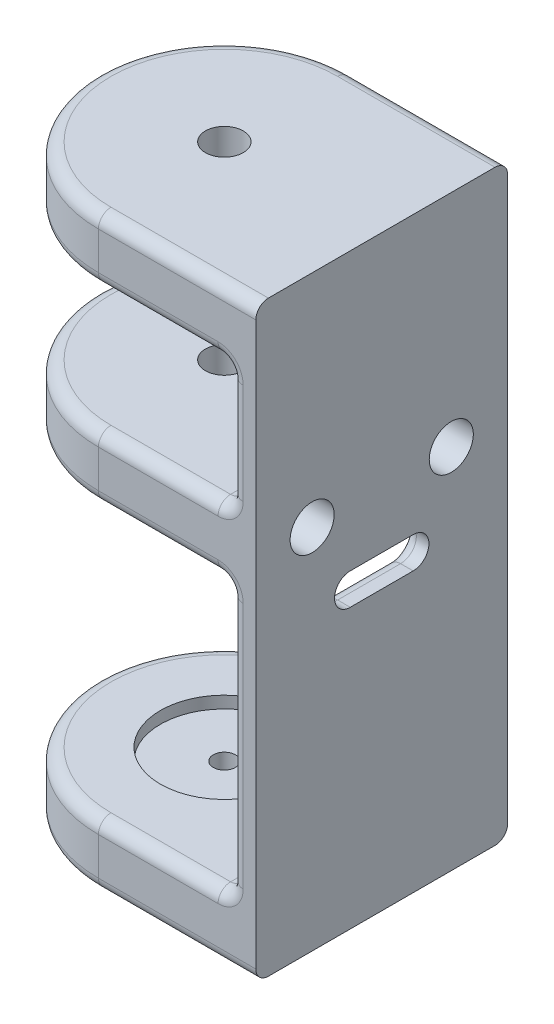
SolidWorks part; units mm, degrees
ref_plane "Front Plane" through (0, 0, 0) normal (0, 0, 1) x (1, 0, 0)
ref_plane "Top Plane" through (0, 0, 0) normal (0, 1, 0) x (1, 0, 0)
ref_plane "Right Plane" through (0, 0, 0) normal (1, 0, 0) x (0, 0, -1)
sketch "Sketch2" plane through (0, 0, 0) normal (0, 1, 0) x (1, 0, 0)
  line L1 (-2, -20) -> (2, -20)
  line L2 (-2, -20) -> (-2, 20)
  line L3 (-2, 20) -> (2, 20)
  line L4 (2, -20) -> (2, 20)
  line L5 (-2, -20) -> (2, 20) construction
  line L6 (-2, 20) -> (2, -20) construction
  point P0 (0, 0)
  dimension "D1" = 4
  dimension "D2" = 40
extrude "Boss-Extrude1" add sketch "Sketch2" along normal blind 93.3
sketch "Sketch1" plane through (0, 93.3, 0) normal (0, 1, 0) x (1, 0, 0)
  line L0 (-2, 20) -> (-2, -20) construction
  line L1 (-23, -20) -> (-2, -20)
  line L3 (-23, 20) -> (-2, 20)
  line L4 (-2, -20) -> (-2, 20)
  line L5 (-23, -20) -> (-2, 20) construction
  line L6 (-23, 20) -> (-2, -20) construction
  line L7 (2, 20) -> (-2, 20) construction
  arc A0 (-23, -20) -> (-23, 20) centre (-23, 0) cw
  point P0 (-12.5, 0)
  dimension "D2" = 40
  dimension "D3" = 21
extrude "Boss-Extrude2" add sketch "Sketch1" against normal blind 10 separate body
sketch "Sketch4" plane through (0, 93.3, 0) normal (0, 1, 0) x (1, 0, 0)
  circle A0 centre (-23, 0) radius 3
  dimension "D1" = 6
extrude "Cut-Extrude4" cut sketch "Sketch4" against normal up to surface (10 mm away) up to face at (-17.5, 83.3, 0)
ref_plane "Plane1" through (0, 46.65, 0) normal (0, 1, 0) x (1, 0, 0)
mirror "Mirror8" about plane through (0, 46.65, 0) normal (0, 1, 0) of "Boss-Extrude2"
ref_plane "Plane3" through (0, 73.3, 0) normal (0, 1, 0) x (1, 0, 0)
mirror "Mirror10" about plane through (0, 73.3, 0) normal (0, 1, 0) of "Boss-Extrude2", "Cut-Extrude4"
combine bodies "Combine2" operation type add bodies to combine 109 107
sketch "Sketch3" plane through (0, 10, 0) normal (0, 1, 0) x (1, 0, 0)
  circle A0 centre (-23, 0) radius 3 construction
  circle A3 centre (-23, 0) radius 10.15
  dimension "D1" = 20.3
extrude "Cut-Extrude3" cut sketch "Sketch3" against normal blind 1.9
sketch "Sketch6" plane through (0, 8.1, 0) normal (0, 1, 0) x (1, 0, 0)
  circle A0 centre (-23, 0) radius 1.75
  circle A3 centre (-23, 0) radius 3 construction
  dimension "D1" = 3.5
extrude "Cut-Extrude6" cut sketch "Sketch6" against normal through all
fillet "Fillet2" radius 2 26 edges at (-2, 63.3, 0) (-2, 10, 0) (-2, 53.3, 0) (-10.5, 0, -20) (-10.5, 0, 20) (-10.5, 93.3, -20) (-10.5, 93.3, 20) (-43, 10, 0) (-43, 53.3, 0) (-43, 63.3, 0) (-12.5, 53.3, 20) (-12.5, 10, 20) (-12.5, 10, -20) (-12.5, 53.3, -20) (-12.5, 63.3, 20) (-12.5, 63.3, -20) (-43, 0, 0) (-2, 31.65, 20) (-2, 31.65, -20) (-43, 93.3, 0) (-43, 83.3, 0) (-12.5, 83.3, -20) (-12.5, 83.3, 20) (-2, 73.3, -20) (-2, 83.3, 0) (-2, 73.3, 20)
sketch "Sketch7" plane through (2, 0, 0) normal (1, 0, 0) x (0, 0, -1)
  line L0 (-18, 93.3) -> (18, 93.3) construction
  line L1 (0, 93.3) -> (0, 0) construction
  line L3 (20, 61.3) -> (20, 55.3) construction
  circle A0 centre (-11.05, 58.3) radius 3.5
  circle A1 centre (11.05, 58.3) radius 3.5
  point P11 (20, 58.3)
  dimension "D1" = 7
  dimension "D2" = 11.05
extrude "Cut-Extrude7" cut sketch "Sketch7" against normal blind 6.1
sketch "Sketch8" plane through (2, 0, 0) normal (1, 0, 0) x (0, 0, -1)
  line L0 (-5, 44.265) -> (5, 44.265) construction
  line L1 (5, 49.265) -> (-5, 49.265) construction
  line L2 (-5, 44.265) -> (5, 44.265)
  line L3 (5, 49.265) -> (-5, 49.265)
  arc A0 (-5, 49.265) -> (-5, 44.265) centre (-5, 46.765) ccw construction
  arc A1 (5, 44.265) -> (5, 49.265) centre (5, 46.765) ccw construction
  arc A2 (-5, 49.265) -> (-5, 44.265) centre (-5, 46.765) ccw
  arc A3 (5, 44.265) -> (5, 49.265) centre (5, 46.765) ccw
extrude "Cut-Extrude8" cut sketch "Sketch8" against normal through all
fillet "Fillet3" radius 2 4 edges at (-2, 49.265, 0) (-2, 46.765, -7.5) (-2, 44.265, 0) (-2, 46.765, 7.5)
